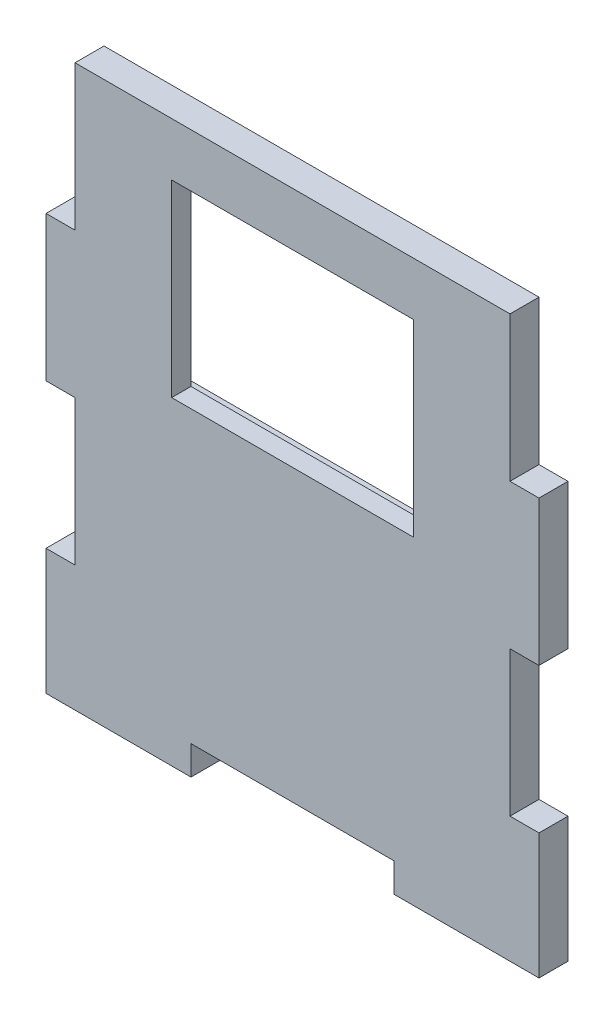
SolidWorks part; units mm, degrees
ref_plane "Front Plane" through (0, 0, 0) normal (0, 0, 1) x (1, 0, 0)
ref_plane "Top Plane" through (0, 0, 0) normal (0, 1, 0) x (1, 0, 0)
ref_plane "Right Plane" through (0, 0, 0) normal (1, 0, 0) x (0, 0, -1)
sketch "Sketch1" plane through (0, 0, 0) normal (0, 1, 0) x (1, 0, 0)
  line L1 (-50, -75) -> (50, -75)
  line L2 (-50, -75) -> (-50, 75)
  line L3 (-50, 75) -> (50, 75)
  line L4 (50, -75) -> (50, 75)
  line L5 (-50, -75) -> (50, 75) construction
  line L6 (-50, 75) -> (50, -75) construction
  point P0 (0, 0)
  dimension "D1" = 100
  dimension "D2" = 150
extrude "Boss-Extrude1" add sketch "Sketch1" along normal blind 150
sketch "Sketch13" plane through (50, 0, 0) normal (1, 0, 0) x (0, 0, -1)
  line L0 (-45, 40) -> (20, 0)
  line L1 (-75, 0) -> (-45, 0)
  line L2 (-75, 0) -> (-75, 40)
  line L3 (-75, 40) -> (-45, 40)
  line L5 (-75, 0) -> (75, 0) construction
  line L8 (-45, 0) -> (20, 0)
  dimension "D1" = 30
  dimension "D2" = 40
  dimension "D3" = 55
extrude "Cut-Extrude7" cut sketch "Sketch13" against normal up to next
shell "Shell1" thickness 5 removed face at (0, 150, 0)
sketch "Sketch3" plane through (0, 0, 0) normal (0, -1, 0) x (1, 0, 0)
  line L1 (50, 45) -> (50, 75) construction
  circle A0 centre (0, 60) radius 4
  circle A1 centre (-5, 50) radius 1.5
  circle A2 centre (5, 50) radius 1.5
  dimension "D3" = 8
  dimension "D4" = 3
  dimension "D5" = 10
  dimension "D7" = 10
  dimension "D8" = 5
  dimension "D1" = 60
  dimension "D2" = 50
extrude "Cut-Extrude2" cut sketch "Sketch3" against normal up to next
sketch "Sketch5" plane through (0, 0, 75) normal (0, 0, 1) x (1, 0, 0)
  line L0 (50, 150) -> (50, 40) construction
  line L1 (-25, 50) -> (25, 50)
  line L2 (-25, 50) -> (-25, 97)
  line L3 (-25, 97) -> (25, 97)
  line L4 (25, 50) -> (25, 97)
  line L5 (-25, 50) -> (25, 97) construction
  line L6 (-25, 97) -> (25, 50) construction
  line L7 (-50, 150) -> (50, 150) construction
  point P0 (0, 73.5)
  dimension "D1" = 50
  dimension "D2" = 47
  dimension "D3" = 50
  dimension "D4" = 76.5
extrude "Boss-Extrude3" add sketch "Sketch5" along normal blind 1
sketch "Sketch8" plane through (0, 0, 75) normal (0, 0, 1) x (1, 0, 0)
  line L0 (-50, 150) -> (-50, 40) construction
  line L1 (-25, 100) -> (25, 100)
  line L2 (-25, 100) -> (-25, 139)
  line L3 (-25, 139) -> (25, 139)
  line L4 (25, 100) -> (25, 139)
  line L5 (-25, 100) -> (25, 139) construction
  line L6 (-25, 139) -> (25, 100) construction
  line L7 (-50, 150) -> (50, 150) construction
  point P0 (0, 119.5)
  dimension "D1" = 50
  dimension "D2" = 39
  dimension "D3" = 50
  dimension "D4" = 50
extrude "Cut-Extrude3" cut sketch "Sketch8" against normal up to next
sketch "Sketch18" plane through (0, 0, 70) normal (0, 0, -1) x (-1, 0, 0)
  line L0 (-25, 139) -> (25, 139) construction
  line L1 (30, 99) -> (-26, 99)
  line L2 (30, 99) -> (30, 140)
  line L3 (30, 140) -> (-26, 140)
  line L4 (-26, 99) -> (-26, 140)
  line L6 (-25, 100) -> (-25, 139) construction
  line L7 (25, 139) -> (25, 100) construction
  dimension "D1" = 1
  dimension "D2" = 41
  dimension "D3" = 1
  dimension "D4" = 5
extrude "Cut-Extrude9" cut sketch "Sketch18" against normal blind 2
sketch "Sketch20" plane through (0, 0, 76) normal (0, 0, 1) x (1, 0, 0)
  line L0 (25, 97) -> (-25, 97) construction
  line L1 (-23, 96) -> (23, 96)
  line L2 (-23, 96) -> (-23, 51)
  line L3 (-23, 51) -> (23, 51)
  line L4 (23, 96) -> (23, 51)
  line L5 (-25, 50) -> (25, 50) construction
  line L6 (25, 50) -> (25, 97) construction
  line L7 (-25, 97) -> (-25, 50) construction
  dimension "D1" = 1
  dimension "D2" = 1
  dimension "D3" = 2
  dimension "D4" = 2
extrude "Cut-Extrude10" cut sketch "Sketch20" against normal blind 15 from offset 4 offset against normal yes
sketch "Sketch21" plane through (0, 45, 0) normal (0, 1, 0) x (1, 0, 0)
  line L1 (9, -52.5) -> (-9, -52.5)
  line L2 (9, -52.5) -> (9, -37.5)
  line L3 (9, -37.5) -> (-9, -37.5)
  line L4 (-9, -52.5) -> (-9, -37.5)
  circle A0 centre (5, -50) radius 1.5 construction
  circle A1 centre (-5, -50) radius 1.5 construction
  dimension "D3" = 4
  dimension "D1" = 4
  dimension "D2" = 2.5
  dimension "D4" = 15
extrude "Cut-Extrude11" cut sketch "Sketch21" against normal blind 2.5
sketch "Sketch22" plane through (-45, 0, 0) normal (1, 0, 0) x (0, 0, -1)
  line L0 (70, 150) -> (-70, 150) construction
  line L5 (70, 150) -> (70, 5) construction
  line L7 (-43.5848, 45) -> (21.4152, 5) construction
  line L8 (10, 150) -> (10, 12.0247)
  line L11 (10, 150) -> (5, 150)
  line L14 (5, 150) -> (5, 15.1017)
  line L15 (5, 15.1017) -> (10, 12.0247)
  dimension "D1" = 60
  dimension "D3" = 5
extrude "Boss-Extrude6" add sketch "Sketch22" along normal blind 5
mirror "Mirror2" about plane through (0, 0, 0) normal (1, 0, 0) of "Boss-Extrude6"
sketch "Sketch23" plane through (-45, 0, 0) normal (1, 0, 0) x (0, 0, -1)
  line L0 (16, 150) -> (21, 150)
  line L1 (70, 150) -> (10, 150) construction
  line L3 (21, 150) -> (21, 5.2555)
  line L4 (21, 5.2555) -> (16, 8.3324)
  line L6 (10, 12.0247) -> (10, 150) construction
  line L7 (16, 150) -> (16, 8.3324)
  line L8 (10, 12.0247) -> (21.4152, 5) construction
  dimension "D1" = 6
  dimension "D2" = 5
extrude "Boss-Extrude7" add sketch "Sketch23" along normal up to next
sketch "Sketch24" plane through (-45, 0, 0) normal (1, 0, 0) x (0, 0, -1)
  line L0 (70, 150) -> (70, 5) construction
  line L1 (70, 135) -> (67, 135)
  line L2 (70, 135) -> (70, 105)
  line L3 (70, 105) -> (67, 105)
  line L4 (67, 135) -> (67, 105)
  line L5 (70, 150) -> (21, 150) construction
  line L6 (70, 5) -> (21.4152, 5) construction
  line L7 (70, 20) -> (67, 20)
  line L8 (70, 20) -> (70, 50)
  line L9 (70, 50) -> (67, 50)
  line L10 (67, 20) -> (67, 50)
  dimension "D1" = 15
  dimension "D2" = 30
  dimension "D3" = 3
  dimension "D4" = 15
extrude "Cut-Extrude12" cut sketch "Sketch24" against normal through all both and the other way through all
sketch "Sketch28" plane through (0, 0, 76) normal (0, 0, 1) x (1, 0, 0)
  line L0 (-25, 73.5) -> (25, 73.5) construction
  line L1 (-25, 97) -> (-25, 50) construction
  line L2 (25, 50) -> (25, 97) construction
  line L3 (-25, 77.511) -> (25, 77.511) construction
  text T0 "SCAN\r\nHERE" font "Impact" height 10
extrude "Cut-Extrude14" cut sketch "Sketch28" against normal blind 1
sketch "Sketch30" plane through (0, 0, -75) normal (0, 0, -1) x (-1, 0, 0)
  text T0 "IBE VAN DE VEIRE\r\nSTEF GIELEN" font "Comic Sans MS" height 5
extrude "Cut-Extrude16" cut sketch "Sketch30" against normal blind 1
sketch "Sketch32" plane through (0, 150, 0) normal (0, 1, 0) x (1, 0, 0)
  line L0 (-50, 75) -> (-50, -75) construction
  line L1 (50, 75) -> (-50, 75) construction
  line L2 (-50, -75) -> (50, -75) construction
  line L3 (50, -75) -> (50, 75) construction
  circle A0 centre (-47, 72) radius 1.225
  circle A1 centre (-47, -72) radius 1.225
  circle A2 centre (47, -72) radius 1.225
  circle A3 centre (47, 72) radius 1.225
  dimension "D1" = 2.45
  dimension "D2" = 3
  dimension "D3" = 3
  dimension "D4" = 2.45
  dimension "D5" = 3
  dimension "D6" = 3
  dimension "D7" = 2.45
  dimension "D8" = 3
  dimension "D9" = 3
  dimension "D10" = 2.45
  dimension "D11" = 3
  dimension "D12" = 3
sketch "Sketch33" plane through (0, 150, 0) normal (0, 1, 0) x (1, 0, 0)
  line L1 (-45, 5) -> (45, 5)
  line L2 (-45, 5) -> (-45, 21)
  line L3 (-45, 21) -> (45, 21)
  line L4 (45, 5) -> (45, 21)
extrude "Cut-Extrude18" cut sketch "Sketch33" against normal blind 40
sketch "Sketch34" plane through (0, 150, 0) normal (0, 1, 0) x (1, 0, 0)
  line L0 (50, 75) -> (-50, 75) construction
  line L1 (-45, 75) -> (50, 75)
  line L2 (-45, 75) -> (-45, -75)
  line L3 (-45, -75) -> (50, -75)
  line L4 (50, 75) -> (50, -75)
sketch "Sketch35" plane through (0, 150, 0) normal (0, 1, 0) x (1, 0, 0)
  line L0 (-50, 75) -> (-50, -75) construction
  line L1 (50, 75) -> (-50, 75)
  line L2 (50, 75) -> (50, -70)
  line L3 (50, -70) -> (-50, -70)
  line L4 (-50, 75) -> (-50, -70)
extrude "Cut-Extrude19" cut sketch "Sketch35" against normal through all
sketch "Sketch36" plane through (0, 0, 76) normal (0, 0, 1) x (1, 0, 0)
  line L1 (-25, 97) -> (25, 97)
  line L2 (-25, 97) -> (-25, 50)
  line L3 (-25, 50) -> (25, 50)
  line L4 (25, 97) -> (25, 50)
sketch "Sketch38" plane through (0, 0, 75) normal (0, 0, 1) x (1, 0, 0)
  line L1 (-50, 150) -> (50, 150)
  line L2 (-50, 150) -> (-50, 40)
  line L3 (-50, 40) -> (50, 40)
  line L4 (50, 150) -> (50, 40)
extrude "Boss-Extrude9" add sketch "Sketch38" along normal blind 1
sketch "Sketch39" plane through (0, 0, 75) normal (0, 0, -1) x (-1, 0, 0)
  line L0 (25, 139) -> (25, 100) construction
  line L1 (-25, 139) -> (25, 139)
  line L2 (-25, 139) -> (-25, 100)
  line L3 (-25, 100) -> (25, 100)
  line L4 (25, 139) -> (25, 100)
  line L5 (25, 100) -> (-25, 100) construction
extrude "Cut-Extrude21" cut sketch "Sketch39" against normal through all
sketch "Sketch41" plane through (50, 0, 0) normal (1, 0, 0) x (0, 0, -1)
  line L1 (-76, 150) -> (-70, 150)
  line L2 (-76, 150) -> (-76, 40)
  line L3 (-76, 40) -> (-70, 40)
  line L4 (-70, 150) -> (-70, 40)
extrude "Boss-Extrude10" add sketch "Sketch41" along normal blind 1
sketch "Sketch42" plane through (-50, 0, 0) normal (-1, 0, 0) x (0, 0, 1)
  line L1 (76, 150) -> (70, 150)
  line L2 (76, 150) -> (76, 40)
  line L3 (76, 40) -> (70, 40)
  line L4 (70, 150) -> (70, 40)
extrude "Boss-Extrude11" add sketch "Sketch42" along normal blind 1
sketch "Sketch43" plane through (0, 0, 76) normal (0, 0, 1) x (1, 0, 0)
  line L1 (51, 150) -> (45, 150)
  line L2 (51, 150) -> (51, 120)
  line L3 (51, 120) -> (45, 120)
  line L4 (45, 150) -> (45, 120)
  dimension "D1" = 6
  dimension "D2" = 30
extrude "Cut-Extrude22" cut sketch "Sketch43" against normal up to next
pattern_linear "LPattern1" count 2 spacing 60 along (0, -1, 0) of "Cut-Extrude22"
ref_plane "Plane1" through (0, 0, 0) normal (1, 0, 0) x (0, 0, -1)
mirror "Mirror3" about plane through (0, 0, 0) normal (1, 0, 0) of "LPattern1", "Cut-Extrude22"
sketch "Sketch45" plane through (0, 40, 0) normal (0, -1, 0) x (1, 0, 0)
  line L0 (-51, 70) -> (51, 70) construction
  line L1 (51, 76) -> (21, 76)
  line L2 (51, 76) -> (51, 70)
  line L3 (51, 70) -> (21, 70)
  line L4 (21, 76) -> (21, 70)
  line L5 (21, 70) -> (21, 76) construction
extrude "Boss-Extrude12" add sketch "Sketch45" along normal blind 6
sketch "Sketch46" plane through (0, 40, 0) normal (0, -1, 0) x (1, 0, 0)
  line L0 (-51, 70) -> (21, 70) construction
  line L1 (-51, 76) -> (-21, 76)
  line L2 (-51, 76) -> (-51, 70)
  line L3 (-51, 70) -> (-21, 70)
  line L4 (-21, 76) -> (-21, 70)
  line L5 (-21, 70) -> (-21, 76) construction
extrude "Boss-Extrude13" add sketch "Sketch46" along normal blind 6
